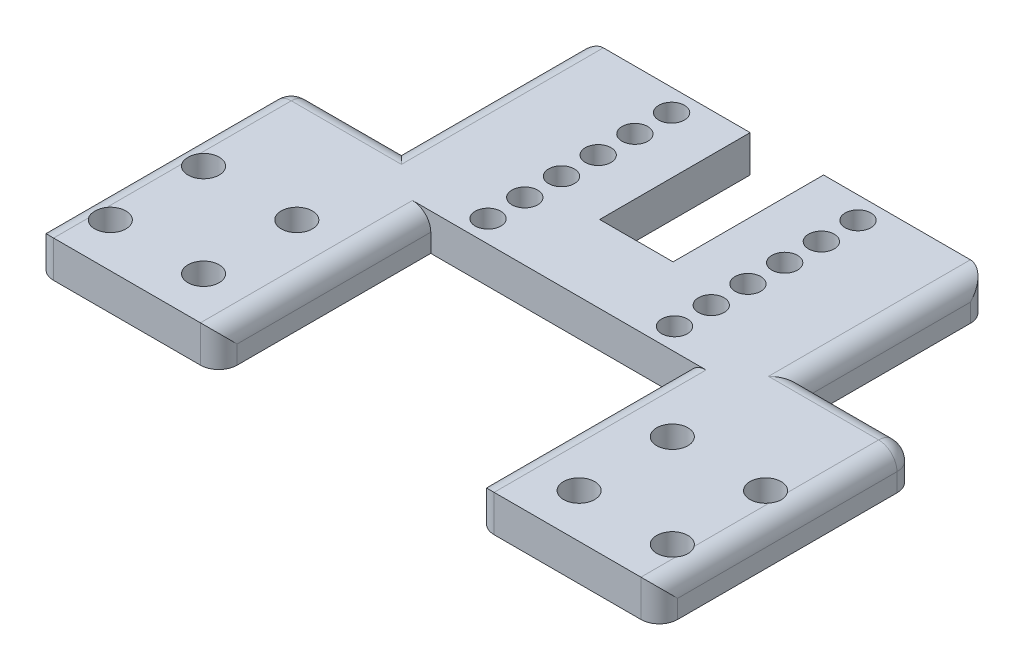
SolidWorks part; units mm, degrees
ref_plane "Front Plane" through (0, 0, 0) normal (0, 0, 1) x (1, 0, 0)
ref_plane "Top Plane" through (0, 0, 0) normal (0, 1, 0) x (1, 0, 0)
ref_plane "Right Plane" through (0, 0, 0) normal (1, 0, 0) x (0, 0, -1)
sketch "Sketch1" plane through (0, 0, 0) normal (0, 1, 0) x (1, 0, 0)
  line L0 (50, 0) -> (50, -62) construction
  line L13 (0, 0) -> (50, 0)
  line L14 (0, 0) -> (0, -119.75)
  line L23 (0, -119.75) -> (50, -119.75)
  line L24 (50, -62) -> (50, -119.75)
  line L25 (50, 0) -> (120, 0)
  line L26 (50, 0) -> (50, -62) construction
  line L27 (50, -62) -> (120, -62)
  line L28 (120, 0) -> (120, -62) construction
  line L29 (120, 0) -> (170, 0)
  line L30 (120, -62) -> (120, -119.75)
  line L31 (120, -119.75) -> (170, -119.75)
  line L32 (170, 0) -> (170, -119.75)
  line L33 (120, 0) -> (120, -62) construction
  dimension "D1" = 119.75
  dimension "D2" = 119.75
  dimension "D3" = 70
  dimension "D4" = 50
  dimension "D5" = 50
  dimension "D6" = 62
extrude "Boss-Extrude1" add sketch "Sketch1" along normal blind 10
sketch "Sketch2" plane through (0, 10, 0) normal (0, 1, 0) x (1, 0, 0)
  line L0 (0, -107.75) -> (170, -107.75) construction
  line L1 (0, 0) -> (0, -119.75) construction
  line L2 (170, -119.75) -> (170, 0) construction
  line L3 (0, -119.75) -> (50, -119.75) construction
  line L4 (0, -82.35) -> (170, -82.35) construction
  line L5 (50, -119.75) -> (50, -62) construction
  line L6 (85, -62) -> (85, -119.75) construction
  line L7 (50, -62) -> (120, -62) construction
  line L8 (120, -119.75) -> (170, -119.75) construction
  circle A0 centre (33.85, -82.35) radius 4.25
  circle A1 centre (8.45, -82.35) radius 4.25
  circle A2 centre (33.85, -107.75) radius 4.25
  circle A3 centre (8.45, -107.75) radius 4.25
  circle A4 centre (161.55, -107.75) radius 4.25
  circle A5 centre (136.15, -107.75) radius 4.25
  circle A6 centre (136.15, -82.35) radius 4.25
  circle A7 centre (161.55, -82.35) radius 4.25
  dimension "D5" = 8.5
  dimension "D6" = 8.5
  dimension "D7" = 8.5
  dimension "D8" = 8.5
  dimension "D1" = 12
  dimension "D2" = 25.4
  dimension "D3" = 16.15
  dimension "D4" = 25.4
  dimension "D9" = 16.15
  dimension "D10" = 25.4
extrude "Cut-Extrude1" cut sketch "Sketch2" against normal up to surface (10 mm away) up to face at (85, 0, 75.375)
sketch "Sketch3" plane through (0, 10, 0) normal (0, 1, 0) x (1, 0, 0)
  line L0 (59.6, -62) -> (59.6, 0) construction
  line L1 (50, -62) -> (120, -62) construction
  line L2 (170, 0) -> (0, 0) construction
  line L3 (110.4, -62) -> (110.4, 0) construction
  line L4 (50, -119.75) -> (50, -62) construction
  line L5 (120, -62) -> (120, -119.75) construction
  circle A0 centre (59.6, -6) radius 3.5
  dimension "D4" = 7
  dimension "D1" = 9.6
  dimension "D2" = 9.6
  dimension "D3" = 6
  dimension "D5" = 50.8
extrude "Cut-Extrude2" cut sketch "Sketch3" against normal up to surface (10 mm away) up to face at (8.45, 0, 86.6)
pattern_linear "LPattern1" count 2 spacing 50.8 along (1, 0, 0) count 6 spacing 10 along (0, 0, 1) of "Cut-Extrude2"
sketch "Sketch4" plane through (0, 10, 0) normal (0, 1, 0) x (1, 0, 0)
  line L1 (0, 0) -> (30, 0)
  line L2 (0, 0) -> (0, -50)
  line L3 (0, -50) -> (30, -50)
  line L4 (30, 0) -> (30, -50)
  line L5 (170, 0) -> (140, 0)
  line L6 (170, 0) -> (170, -50)
  line L7 (170, -50) -> (140, -50)
  line L8 (140, 0) -> (140, -50)
  dimension "D4" = 50
  dimension "D1" = 30
  dimension "D2" = 50
  dimension "D3" = 30
extrude "Cut-Extrude3" cut sketch "Sketch4" against normal up to surface (10 mm away) up to face at (110.4, 0, 9.5)
fillet "Fillet1" radius 5 16 edges at (170, 5, 50) (140, 5, 0) (30, 5, 0) (0, 5, 50) (170, 10, 84.875) (120, 10, 90.875) (0, 10, 84.875) (50, 10, 90.875) (170, 5, 119.75) (120, 5, 119.75) (50, 5, 119.75) (0, 5, 119.75) (15, 10, 50) (155, 10, 50) (140, 10, 25) (30, 10, 25)
sketch "Sketch5" plane through (0, 10, 0) normal (0, 1, 0) x (1, 0, 0)
  line L0 (135, 0) -> (35, 0) construction
  line L1 (75, 0) -> (95, 0)
  line L2 (75, 0) -> (75, -41)
  line L3 (75, -41) -> (95, -41) construction
  line L4 (95, 0) -> (95, -41)
  line L5 (75, -41) -> (95, -41)
  line L6 (35, 0) -> (35, -55) construction
  line L7 (135, -55) -> (135, 0) construction
  line L8 (45, -62) -> (125, -62) construction
  line L9 (35, -41) -> (75, -41) construction
  line L10 (95, -41) -> (135, -41) construction
  circle A0 centre (59.6, -6) radius 3.5 construction
  dimension "D1" = 21
  dimension "D2" = 20
  dimension "D3" = 15.4
extrude "Cut-Extrude4" cut sketch "Sketch5" against normal up to surface (10 mm away) up to face at (110.4, 0, 9.5)
equation "\"D2@Sketch1\"=\"D1@Sketch1\""
equation "\"D6@Sketch2\"=\"D5@Sketch2\""
equation "\"D7@Sketch2\"=\"D5@Sketch2\""
equation "\"D8@Sketch2\"=\"D5@Sketch2\""
equation "\"D9@Sketch2\"=\"D3@Sketch2\""
equation "\"D10@Sketch2\"=\"D4@Sketch2\""
equation "\"D3@Sketch4\"=\"D1@Sketch4\""
equation "\"D4@Sketch4\"=\"D2@Sketch4\""
